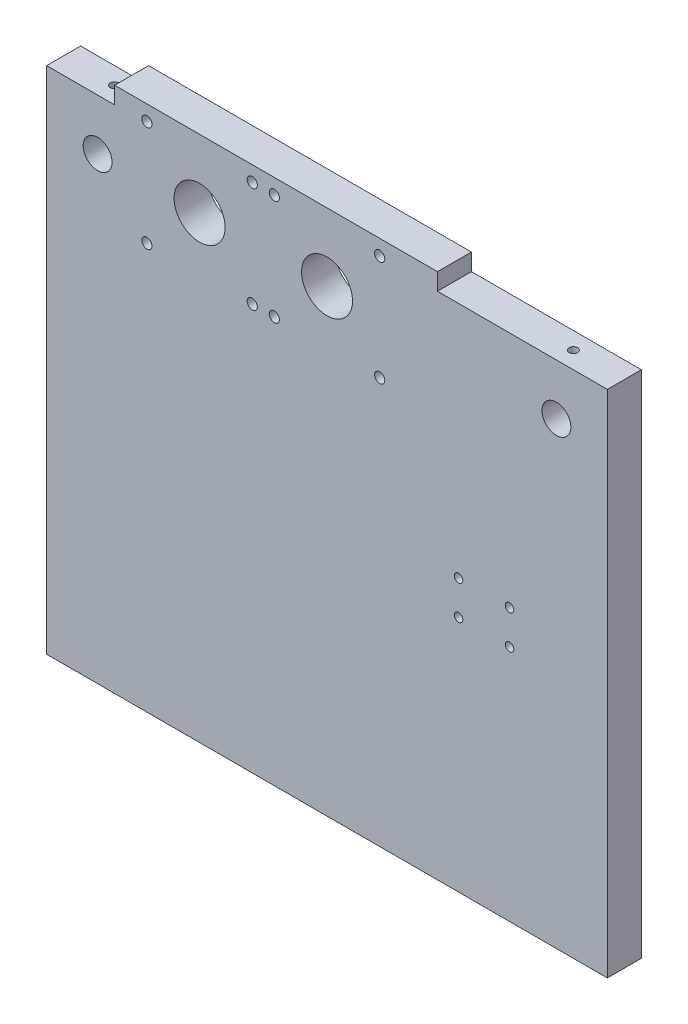
SolidWorks part; units mm, degrees
ref_plane "Plan de face" through (0, 0, 0) normal (0, 0, 1) x (1, 0, 0)
ref_plane "Plan de dessus" through (0, 0, 0) normal (0, 1, 0) x (1, 0, 0)
ref_plane "Plan de droite" through (0, 0, 0) normal (1, 0, 0) x (0, 0, -1)
sketch "Esquisse1" plane through (0, 0, 0) normal (0, 0, 1) x (1, 0, 0)
  line L1 (-82.5, -75) -> (82.5, -75)
  line L2 (-82.5, -75) -> (-82.5, 75)
  line L3 (-82.5, 75) -> (82.5, 75)
  line L4 (82.5, -75) -> (82.5, 75)
  line L5 (-82.5, -75) -> (82.5, 75) construction
  line L6 (-82.5, 75) -> (82.5, -75) construction
  point P0 (0, 0)
  point P11 (0, 0)
  point P12 (1.0519, 85)
  point P13 (37.0436, 89.7341)
  point P20 (-37.536, 85)
  point P21 (0, 0)
  dimension "D1" = 150
  dimension "D2" = 165
extrude "Boss.-Extru.1" add sketch "Esquisse1" along normal blind 10
sketch "Esquisse2" plane through (0, 0, 10) normal (0, 0, 1) x (1, 0, 0)
  line L0 (-82.5, 75) -> (-82.5, -75) construction
  line L2 (82.5, 75) -> (-82.5, 75) construction
  line L3 (0, 14.3557) -> (0, 51.8048) construction
  circle A0 centre (-67.5, 60) radius 4.25
  circle A1 centre (67.5, 60) radius 4.25
  dimension "D1" = 8.5
  dimension "D2" = 15
  dimension "D3" = 15
extrude "Enlèv. mat.-Extru.1" cut sketch "Esquisse2" against normal blind 10
sketch "Esquisse4" plane through (0, 0, 10) normal (0, 0, 1) x (1, 0, 0)
  line L0 (-15.5, 75.5) -> (0.6525, 75.5) construction
  line L1 (0.6525, 75.5) -> (0.6525, 68.0179) construction
  line L2 (-15.5, 75.5) -> (15.5, 44.5) construction
  line L3 (-67.5, 60) -> (67.1307, 60) construction
  line L5 (-53, 75.5) -> (-27.6278, 75.5) construction
  line L6 (-27.6278, 75.5) -> (-27.6278, 68.0179) construction
  line L7 (-53, 75.5) -> (-22, 44.5) construction
  circle A0 centre (-15.5, 75.5) radius 1.5
  circle A1 centre (15.5, 75.5) radius 1.5
  circle A2 centre (15.5, 44.5) radius 1.5
  circle A3 centre (-15.5, 44.5) radius 1.5
  circle A4 centre (0, 60) radius 7.5
  circle A5 centre (-53, 75.5) radius 1.5
  circle A6 centre (-22, 75.5) radius 1.5
  circle A7 centre (-22, 44.5) radius 1.5
  circle A8 centre (-53, 44.5) radius 1.5
  circle A9 centre (-37.5, 60) radius 7.5
  point P6 (0, 0)
  point P13 (-10.9925, 68.0179)
  point P16 (-11.6342, 75)
  point P17 (-12.2867, 60)
  point P19 (-4.6489, 59.5)
  point P20 (-1.9734, 64.263)
  point P34 (0, 0)
  point P35 (0, 0)
  point P36 (-46.2564, 60)
  point P37 (0, 0)
  point P38 (0, 0)
  point P39 (0, 0)
  dimension "D1" = 3
  dimension "D4" = 15
  dimension "D5" = 31
  dimension "D6" = 31
  dimension "D7" = 15
  dimension "D9" = 31
  dimension "D10" = 37.5
  dimension "D8" = 31
  dimension "D2" = 2
  dimension "D3" = 2
sketch "Esquisse5" plane through (0, 75, 0) normal (0, 1, 0) x (1, 0, 0)
  line L0 (-67.5, -10) -> (67.1307, -10) construction
  line L1 (-62.5, -10) -> (32.5, -10)
  line L2 (-62.5, -10) -> (-62.5, 0)
  line L3 (-62.5, 0) -> (32.5, 0)
  line L4 (32.5, -10) -> (32.5, 0)
  line L5 (82.5, 0) -> (-82.5, 0) construction
  line L6 (-82.5, -10) -> (-82.5, 0) construction
  line L7 (82.5, -10) -> (82.5, 0) construction
  dimension "D1" = 20
  dimension "D2" = 50
extrude "Boss.-Extru.2" add sketch "Esquisse5" along normal blind 5
extrude "Enlèv. mat.-Extru.2" cut sketch "Esquisse4" against normal blind 15
sketch "Esquisse6" plane through (0, 0, 10) normal (0, 0, 1) x (1, 0, 0)
  line L0 (38.7151, 5) -> (53.7151, 5) construction
  line L1 (53.7151, 5) -> (53.7151, -5) construction
  line L2 (53.7151, -5) -> (38.7151, -5) construction
  line L3 (38.7151, -5) -> (38.7151, 5) construction
  line L4 (7.5, 60) -> (63.25, 60) construction
  line L5 (0, 0) -> (82.5, 0) construction
  line L6 (82.5, -75) -> (82.5, 75) construction
  circle A0 centre (38.7151, 5) radius 1.25
  circle A1 centre (53.7151, 5) radius 1.25
  circle A2 centre (53.7151, -5) radius 1.25
  circle A3 centre (38.7151, -5) radius 1.25
  circle A4 centre (0, 60) radius 7.5 construction
  circle A5 centre (67.5, 60) radius 4.25 construction
  point P9 (82.5, 0)
  point P16 (38.7151, 5.42)
  point P22 (0, 0)
  point P23 (0, 0)
  dimension "D1" = 2.5
  dimension "D5" = 2.5
  dimension "D6" = 2.5
  dimension "D7" = 2.5
  dimension "D2" = 15
  dimension "D3" = 10
  dimension "D4" = 10
  dimension "D8" = 5
extrude "Enlèv. mat.-Extru.3" cut sketch "Esquisse6" against normal blind 10 contours A0 | A3 | A2 | A1 region at (38.7151, 5, 10) region at (53.7151, -5, 10) region at (38.7151, -5, 10)
sketch "Esquisse7" plane through (0, 0, 0) normal (0, 0, -1) x (-1, 0, 0)
  line L1 (-15, -10) -> (15, -10)
  line L2 (-15, -10) -> (-15, 10)
  line L3 (-15, 10) -> (15, 10)
  line L4 (15, -10) -> (15, 10)
  line L5 (-15, -10) -> (15, 10) construction
  line L6 (-15, 10) -> (15, -10) construction
  point P0 (0, 0)
  dimension "D1" = 30
  dimension "D2" = 20
extrude "Boss.-Extru.3" add sketch "Esquisse7" along normal blind 30
sketch "Esquisse8" plane through (0, 10, 0) normal (0, 1, 0) x (1, 0, 0)
  line L0 (32.5, 0) -> (-62.5, 0) construction
  circle A0 centre (0, 15) radius 11.5
  circle A1 centre (0, 15) radius 5.5
  circle A2 centre (0, 23) radius 2
  circle A3 centre (8, 15) radius 2
  circle A4 centre (0, 7) radius 2
  circle A5 centre (-8, 15) radius 2
  point P16 (0, 15)
  dimension "D1" = 23
  dimension "D2" = 11
  dimension "D4" = 4
  dimension "D5" = 8
  dimension "D3" = 15
  dimension "D6" = 4
extrude "Enlèv. mat.-Extru.4" cut sketch "Esquisse8" against normal blind 30 contours A1 | A5 | A2 | A3 | A4 region at (0, 10, -15)
extrude "Enlèv. mat.-Extru.5" cut sketch "Esquisse8<4>" against normal blind 5
sketch "Esquisse8<4>" plane through (0, 10, 0) normal (0, 1, 0) x (1, 0, 0) same geometry as "Esquisse8"
sketch "Esquisse9" plane through (0, 75, 0) normal (0, 1, 0) x (1, 0, 0)
  line L0 (82.5, -5) -> (56.7618, -5) construction
  line L1 (82.5, -10) -> (82.5, 0) construction
  line L3 (0, -22) -> (0, 22) construction
  circle A0 centre (67.5, -5) radius 1.25
  circle A1 centre (-67.5, -5) radius 1.25
  dimension "D1" = 2.5
  dimension "D2" = 15
extrude "Enlèv. mat.-Extru.6" cut sketch "Esquisse9" against normal blind 15
